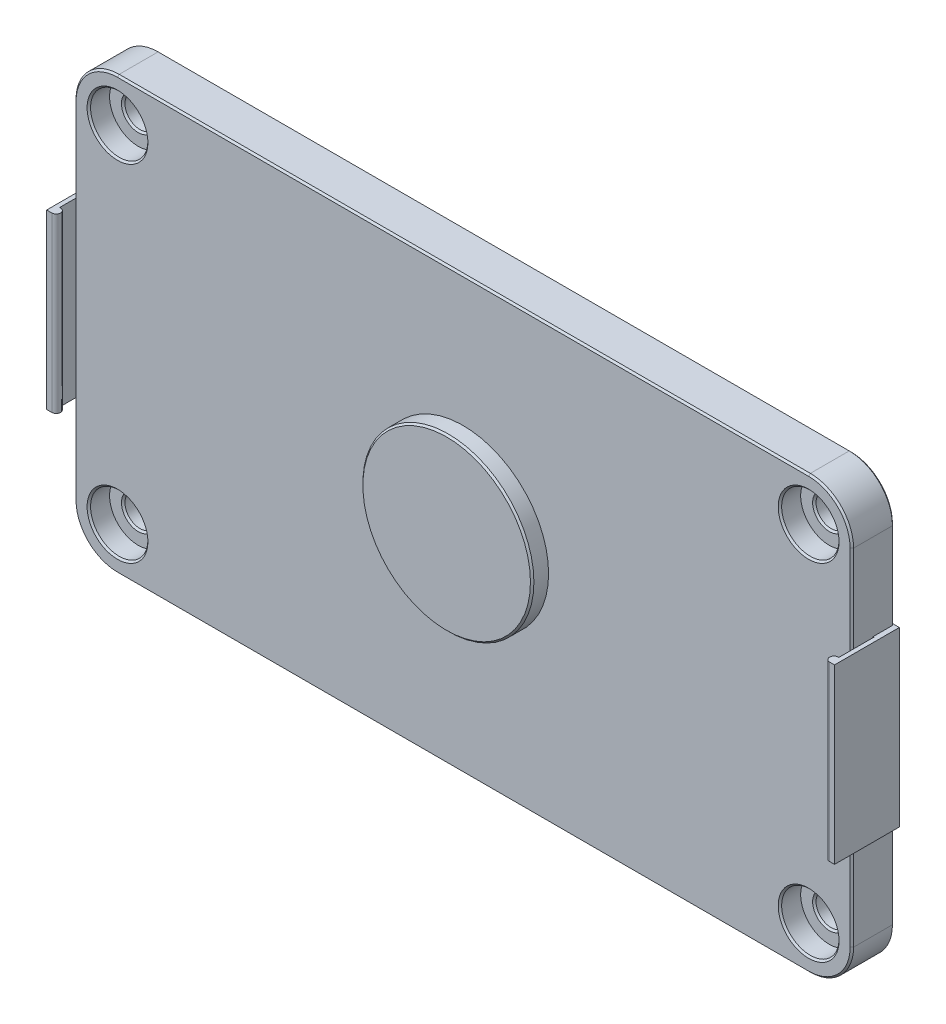
SolidWorks part; units mm, degrees
material "ABS"
ref_plane "Front Plane" through (0, 0, 0) normal (0, 0, 1) x (1, 0, 0)
ref_plane "Top Plane" through (0, 0, 0) normal (0, 1, 0) x (1, 0, 0)
ref_plane "Right Plane" through (0, 0, 0) normal (1, 0, 0) x (0, 0, -1)
sketch "Sketch1" plane through (0, 0, 0) normal (0, 0, 1) x (1, 0, 0)
  line L1 (-50.8, -31.75) -> (50.8, -31.75)
  line L2 (-57.15, -25.4) -> (-57.15, 25.4)
  line L3 (-50.8, 31.75) -> (50.8, 31.75)
  line L4 (57.15, -25.4) -> (57.15, 25.4)
  line L5 (-57.15, -31.75) -> (57.15, 31.75) construction
  line L6 (-57.15, 31.75) -> (57.15, -31.75) construction
  arc A0 (50.8, -31.75) -> (57.15, -25.4) centre (50.8, -25.4) ccw
  arc A1 (50.8, 31.75) -> (57.15, 25.4) centre (50.8, 25.4) cw
  arc A2 (-57.15, 25.4) -> (-50.8, 31.75) centre (-50.8, 25.4) cw
  arc A3 (-50.8, -31.75) -> (-57.15, -25.4) centre (-50.8, -25.4) cw
  circle A4 centre (-50.8, -25.4) radius 2.2098
  circle A5 centre (-50.8, 25.4) radius 2.2098
  circle A6 centre (50.8, 25.4) radius 2.2098
  circle A7 centre (50.8, -25.4) radius 2.2098
  point P0 (0, 0)
  dimension "D3" = 6.35
  dimension "D4" = 4.4196
  dimension "D1" = 114.3
  dimension "D2" = 63.5
extrude "Boss-Extrude1" add sketch "Sketch1" along normal blind 6.223
sketch "Sketch2" plane through (0, 0, 6.223) normal (0, 0, 1) x (1, 0, 0)
  circle A0 centre (-50.8, 25.4) radius 4.2164
  circle A1 centre (50.8, 25.4) radius 4.2164
  circle A2 centre (50.8, -25.4) radius 4.2164
  circle A3 centre (-50.8, -25.4) radius 4.2164
  dimension "D1" = 8.4328
extrude "Cut-Extrude1" cut sketch "Sketch2" against normal blind 3.048
sketch "Sketch4" plane through (0, 0, 0) normal (0, 0, 1) x (1, 0, 0)
  line L0 (-57.15, 25.4) -> (-57.15, -25.4) construction
  line L1 (-57.15, 12.7) -> (-57.912, 12.7)
  line L2 (-57.15, 12.7) -> (-57.15, -12.7)
  line L3 (-57.15, -12.7) -> (-57.912, -12.7)
  line L4 (-57.912, 12.7) -> (-57.912, -12.7)
  line L5 (0, -3.4226) -> (0, 3.4226) construction
  line L6 (57.15, -12.7) -> (57.912, -12.7)
  line L7 (57.912, 12.7) -> (57.912, -12.7)
  line L8 (57.15, 12.7) -> (57.912, 12.7)
  line L9 (57.15, 12.7) -> (57.15, -12.7)
  point P6 (-57.15, 0)
  dimension "D1" = 25.4
  dimension "D2" = 0.762
extrude "Boss-Extrude2" add sketch "Sketch4" along normal blind 3.1115
sketch "Sketch5" plane through (0, -12.7, 0) normal (0, -1, 0) x (1, 0, 0)
  line L0 (-57.277, 3.1115) -> (-57.912, 3.1115)
  line L1 (-57.277, 8.255) -> (-57.15, 8.255)
  line L2 (-57.912, 3.1115) -> (-57.912, 9.525)
  line L3 (-57.912, 9.525) -> (-57.15, 9.525)
  line L6 (-57.277, 8.255) -> (-57.277, 3.1115)
  line L7 (-57.15, 6.223) -> (-57.15, 0) construction
  line L12 (-57.912, 3.1115) -> (-57.15, 3.1115) construction
  line L13 (-57.912, 3.1115) -> (-57.912, 0) construction
  line L14 (0, -3.4226) -> (0, 3.4226) construction
  line L15 (57.912, 9.525) -> (57.15, 9.525)
  line L16 (57.912, 3.1115) -> (57.912, 9.525)
  line L17 (57.277, 3.1115) -> (57.912, 3.1115)
  line L18 (57.277, 8.255) -> (57.277, 3.1115)
  line L19 (-50.8, 6.223) -> (-57.15, 6.223) construction
  arc A2 (57.15, 9.525) -> (57.277, 8.255) centre (57.1955, 8.8882) ccw
  arc A3 (-57.15, 8.255) -> (-57.15, 9.525) centre (-57.15, 8.89) ccw
  point P25 (-57.0762, 8.1796)
  dimension "D2" = 2.667
  dimension "D3" = 0.635
  dimension "D1" = 0.635
extrude "Boss-Extrude3" add sketch "Sketch5" against normal up to surface (25.4 mm away) up to face at (-57.531, 12.7, 1.5557)
sketch "Sketch6" plane through (0, 0, 6.223) normal (0, 0, 1) x (1, 0, 0)
  circle A0 centre (0, 0) radius 12.573
  dimension "D1" = 25.146
extrude "Boss-Extrude4" add sketch "Sketch6" along normal blind 2.413
chamfer "Chamfer1" distance 0.254 angle 45 27 edges at (12.573, 0, 8.636) (-57.15, -19.05, 0) (57.15, -19.05, 0) (-55.2901, -29.8901, 0) (55.2901, -29.8901, 0) (0, -31.75, 0) (0, 31.75, 6.223) (-55.2901, 29.8901, 6.223) (55.2901, 29.8901, 6.223) (-57.15, 0, 6.223) (57.15, 0, 6.223) (-55.2901, -29.8901, 6.223) (55.2901, -29.8901, 6.223) (0, -31.75, 6.223) (-46.5836, -25.4, 6.223) (-46.5836, 25.4, 6.223) (55.0164, 25.4, 6.223) (55.0164, -25.4, 6.223) (53.0098, 25.4, 3.175) (-48.5902, 25.4, 3.175) (-48.5902, -25.4, 3.175) (53.0098, -25.4, 3.175) (57.15, 19.05, 0) (-57.15, 19.05, 0) (55.2901, 29.8901, 0) (-55.2901, 29.8901, 0) (0, 31.75, 0)
equation "\"wall-thickness\"= .2"
equation "\"tolerance\"= 0.005"
equation "\"D1@Boss-Extrude1\"= .115 + .125 + \"tolerance\""
equation "\"D4@Sketch1\"=.164 + \"tolerance\" * 2"
equation "\"D1@Sketch2\"= .322 + \"tolerance\" * 2"
equation "\"D1@Cut-Extrude1\"= .115 + \"tolerance\""
equation "\"D2@Sketch4\"=.025 + \"tolerance\""
equation "\"D1@Boss-Extrude2\"= \"D1@Boss-Extrude1\" / 2"
equation "\"D1@Sketch6\"=1-\"tolerance\"*2"
equation "\"D1@Boss-Extrude4\"=.1-\"tolerance\""
